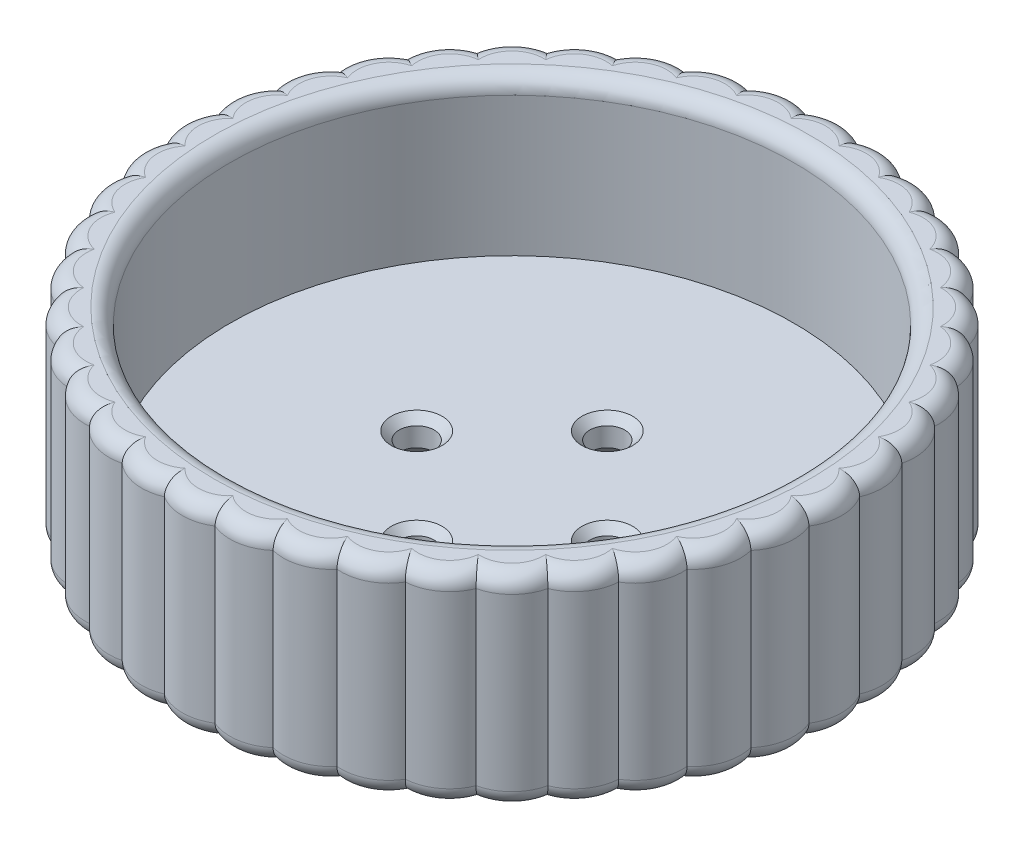
SolidWorks part; units mm, degrees
ref_plane "Front Plane" through (0, 0, 0) normal (0, 0, 1) x (1, 0, 0)
ref_plane "Top Plane" through (0, 0, 0) normal (0, 1, 0) x (1, 0, 0)
ref_plane "Right Plane" through (0, 0, 0) normal (1, 0, 0) x (0, 0, -1)
sketch "Sketch1" plane through (0, 0, 0) normal (0, 1, 0) x (1, 0, 0)
  line L0 (0, 0) -> (6, 0) construction
  line L1 (0, 0) -> (4.2426, 4.2426) construction
  arc A0 (-5.8992, -1.0954) -> (-1.0954, -5.8992) centre (0, 0) ccw
  circle A1 centre (0, 6) radius 1.1
  circle A2 centre (0, -6) radius 1.1
  circle A3 centre (-6, 0) radius 1.1
  circle A4 centre (6, 0) radius 1.1
  arc A5 (-1.0954, 5.8992) -> (-5.8992, 1.0954) centre (0, 0) ccw
  arc A6 (5.8992, 1.0954) -> (1.0954, 5.8992) centre (0, 0) ccw
  arc A7 (1.0954, -5.8992) -> (5.8992, -1.0954) centre (0, 0) ccw
  circle A8 centre (0, 0) radius 17.75
  circle A9 centre (0, 0) radius 20.75
  dimension "D1" = 3
extrude "Boss-Extrude1" add sketch "Sketch1" along normal blind 3 contours A8 A7 A2 A0 A3 A5 A1 A6 A4 | A2 A7 A4 A6 A1 A5 A3 A0 region at (0, 0, 0) region at (-17.248, 0, 0)
extrude "Boss-Extrude2" add sketch "Sketch1<6>" along normal blind 12.75 contours A9 A8 region at (-20.1631, 0, 0)
sketch "Sketch1<6>" plane through (0, 0, 0) normal (0, 1, 0) x (1, 0, 0) same geometry as "Sketch1"
chamfer "Chamfer1" distance 1.3 angle 45 4 edges at (-6, 0, 1.1) (0, 0, -4.9) (6, 0, 1.1) (0, 0, 7.1)
fillet "Fillet3" radius 1 1 edges at (0, 12.75, 17.75)
chamfer "Chamfer2" distance 0.5 angle 45 4 edges at (6, 3, 1.1) (0, 3, 7.1) (-6, 3, 1.1) (0, 3, -4.9)
sketch "Sketch3" plane through (0, 0, 0) normal (0, -1, 0) x (1, 0, 0)
  arc A0 (-12.3979, -12.7025) -> (-15.912, -7.8658) centre (-14.3601, -10.4332) ccw
  circle A1 centre (0, 0) radius 22
  arc A2 (-1.5968, -20.2897) -> (1.5968, -20.2897) centre (0, -17.75) ccw
  circle A3 centre (0, 0) radius 17.75
  arc A4 (-4.7512, -19.7901) -> (-1.5968, -20.2897) centre (-2.7767, -17.5315) ccw
  arc A5 (-7.7885, -18.8032) -> (-4.7512, -19.7901) centre (-5.4851, -16.8813) ccw
  arc A6 (-10.6341, -17.3533) -> (-7.7885, -18.8032) centre (-8.0583, -15.8154) ccw
  arc A7 (-13.2179, -15.4761) -> (-10.6341, -17.3533) centre (-10.4332, -14.3601) ccw
  arc A8 (-15.4761, -13.2179) -> (-13.2179, -15.4761) centre (-12.5511, -12.5511) ccw
  arc A9 (-17.3533, -10.6341) -> (-15.4761, -13.2179) centre (-14.3601, -10.4332) ccw
  arc A10 (-18.8032, -7.7885) -> (-17.3533, -10.6341) centre (-15.8154, -8.0583) ccw
  arc A11 (-19.7901, -4.7512) -> (-18.8032, -7.7885) centre (-16.8813, -5.4851) ccw
  arc A12 (-20.2897, -1.5968) -> (-19.7901, -4.7512) centre (-17.5315, -2.7767) ccw
  arc A13 (-20.2897, 1.5968) -> (-20.2897, -1.5968) centre (-17.75, 0) ccw
  arc A14 (-19.7901, 4.7512) -> (-20.2897, 1.5968) centre (-17.5315, 2.7767) ccw
  arc A15 (-18.8032, 7.7885) -> (-19.7901, 4.7512) centre (-16.8813, 5.4851) ccw
  arc A16 (-17.3533, 10.6341) -> (-18.8032, 7.7885) centre (-15.8154, 8.0583) ccw
  arc A17 (-15.4761, 13.2179) -> (-17.3533, 10.6341) centre (-14.3601, 10.4332) ccw
  arc A18 (-13.2179, 15.4761) -> (-15.4761, 13.2179) centre (-12.5511, 12.5511) ccw
  arc A19 (-10.6341, 17.3533) -> (-13.2179, 15.4761) centre (-10.4332, 14.3601) ccw
  arc A20 (-7.7885, 18.8032) -> (-10.6341, 17.3533) centre (-8.0583, 15.8154) ccw
  arc A21 (-4.7512, 19.7901) -> (-7.7885, 18.8032) centre (-5.4851, 16.8813) ccw
  arc A22 (-1.5968, 20.2897) -> (-4.7512, 19.7901) centre (-2.7767, 17.5315) ccw
  arc A23 (1.5968, 20.2897) -> (-1.5968, 20.2897) centre (0, 17.75) ccw
  arc A24 (4.7512, 19.7901) -> (1.5968, 20.2897) centre (2.7767, 17.5315) ccw
  arc A25 (7.7885, 18.8032) -> (4.7512, 19.7901) centre (5.4851, 16.8813) ccw
  arc A26 (10.6341, 17.3533) -> (7.7885, 18.8032) centre (8.0583, 15.8154) ccw
  arc A27 (13.2179, 15.4761) -> (10.6341, 17.3533) centre (10.4332, 14.3601) ccw
  arc A28 (15.4761, 13.2179) -> (13.2179, 15.4761) centre (12.5511, 12.5511) ccw
  arc A29 (17.3533, 10.6341) -> (15.4761, 13.2179) centre (14.3601, 10.4332) ccw
  arc A30 (18.8032, 7.7885) -> (17.3533, 10.6341) centre (15.8154, 8.0583) ccw
  arc A31 (19.7901, 4.7512) -> (18.8032, 7.7885) centre (16.8813, 5.4851) ccw
  arc A32 (16.8134, 5.6895) -> (17.7487, -0.2154) centre (17.5315, 2.7767) ccw
  arc A33 (17.4965, 2.9893) -> (17.4965, -2.9893) centre (17.75, 0) ccw
  arc A34 (19.7901, -4.7512) -> (20.2897, -1.5968) centre (17.5315, -2.7767) ccw
  arc A35 (18.8032, -7.7885) -> (19.7901, -4.7512) centre (16.8813, -5.4851) ccw
  arc A36 (17.3533, -10.6341) -> (18.8032, -7.7885) centre (15.8154, -8.0583) ccw
  arc A37 (15.4761, -13.2179) -> (17.3533, -10.6341) centre (14.3601, -10.4332) ccw
  arc A38 (13.2179, -15.4761) -> (15.4761, -13.2179) centre (12.5511, -12.5511) ccw
  arc A39 (10.6341, -17.3533) -> (13.2179, -15.4761) centre (10.4332, -14.3601) ccw
  arc A40 (10.6067, -14.2324) -> (5.2798, -16.9466) centre (8.0583, -15.8154) ccw
  arc A41 (4.7512, -19.7901) -> (7.7885, -18.8032) centre (5.4851, -16.8813) ccw
  arc A42 (1.5968, -20.2897) -> (4.7512, -19.7901) centre (2.7767, -17.5315) ccw
  arc A43 (15.7164, 8.2497) -> (17.5639, 2.5637) centre (16.8813, 5.4851) ccw
  arc A44 (14.2324, 10.6067) -> (16.9466, 5.2798) centre (15.8154, 8.0583) ccw
  arc A45 (12.3979, 12.7025) -> (15.912, 7.8658) centre (14.3601, 10.4332) ccw
  arc A46 (10.2581, 14.4856) -> (14.4856, 10.2581) centre (12.5511, 12.5511) ccw
  arc A47 (7.8658, 15.912) -> (12.7025, 12.3979) centre (10.4332, 14.3601) ccw
  arc A48 (5.2798, 16.9466) -> (10.6067, 14.2324) centre (8.0583, 15.8154) ccw
  arc A49 (2.5637, 17.5639) -> (8.2497, 15.7164) centre (5.4851, 16.8813) ccw
  arc A50 (-0.2154, 17.7487) -> (5.6895, 16.8134) centre (2.7767, 17.5315) ccw
  arc A51 (-2.9893, 17.4965) -> (2.9893, 17.4965) centre (0, 17.75) ccw
  arc A52 (-5.6895, 16.8134) -> (0.2154, 17.7487) centre (-2.7767, 17.5315) ccw
  arc A53 (-8.2497, 15.7164) -> (-2.5637, 17.5639) centre (-5.4851, 16.8813) ccw
  arc A54 (-10.6067, 14.2324) -> (-5.2798, 16.9466) centre (-8.0583, 15.8154) ccw
  arc A55 (-12.7025, 12.3979) -> (-7.8658, 15.912) centre (-10.4332, 14.3601) ccw
  arc A56 (-14.4856, 10.2581) -> (-10.2581, 14.4856) centre (-12.5511, 12.5511) ccw
  arc A57 (-15.912, 7.8658) -> (-12.3979, 12.7025) centre (-14.3601, 10.4332) ccw
  arc A58 (-16.9466, 5.2798) -> (-14.2324, 10.6067) centre (-15.8154, 8.0583) ccw
  arc A59 (-17.5639, 2.5637) -> (-15.7164, 8.2497) centre (-16.8813, 5.4851) ccw
  arc A60 (-17.7487, -0.2154) -> (-16.8134, 5.6895) centre (-17.5315, 2.7767) ccw
  arc A61 (-17.4965, -2.9893) -> (-17.4965, 2.9893) centre (-17.75, 0) ccw
  arc A62 (-16.8134, -5.6895) -> (-17.7487, 0.2154) centre (-17.5315, -2.7767) ccw
  arc A63 (-15.7164, -8.2497) -> (-17.5639, -2.5637) centre (-16.8813, -5.4851) ccw
  arc A64 (-14.2324, -10.6067) -> (-16.9466, -5.2798) centre (-15.8154, -8.0583) ccw
  arc A65 (-10.2581, -14.4856) -> (-14.4856, -10.2581) centre (-12.5511, -12.5511) ccw
  arc A66 (-7.8658, -15.912) -> (-12.7025, -12.3979) centre (-10.4332, -14.3601) ccw
  arc A67 (-5.2798, -16.9466) -> (-10.6067, -14.2324) centre (-8.0583, -15.8154) ccw
  arc A68 (-2.5637, -17.5639) -> (-8.2497, -15.7164) centre (-5.4851, -16.8813) ccw
  arc A69 (0.2154, -17.7487) -> (-5.6895, -16.8134) centre (-2.7767, -17.5315) ccw
  arc A70 (2.9893, -17.4965) -> (-2.9893, -17.4965) centre (0, -17.75) ccw
  arc A71 (5.6895, -16.8134) -> (-0.2154, -17.7487) centre (2.7767, -17.5315) ccw
  arc A72 (8.2497, -15.7164) -> (2.5637, -17.5639) centre (5.4851, -16.8813) ccw
  arc A73 (12.7025, -12.3979) -> (7.8658, -15.912) centre (10.4332, -14.3601) ccw
  arc A74 (7.7885, -18.8032) -> (10.6341, -17.3533) centre (8.0583, -15.8154) ccw
  arc A75 (14.4856, -10.2581) -> (10.2581, -14.4856) centre (12.5511, -12.5511) ccw
  arc A76 (15.912, -7.8658) -> (12.3979, -12.7025) centre (14.3601, -10.4332) ccw
  arc A77 (16.9466, -5.2798) -> (14.2324, -10.6067) centre (15.8154, -8.0583) ccw
  arc A78 (17.5639, -2.5637) -> (15.7164, -8.2497) centre (16.8813, -5.4851) ccw
  arc A79 (20.2897, -1.5968) -> (20.2897, 1.5968) centre (17.75, 0) ccw
  arc A80 (17.7487, 0.2154) -> (16.8134, -5.6895) centre (17.5315, -2.7767) ccw
  arc A81 (20.2897, 1.5968) -> (19.7901, 4.7512) centre (17.5315, 2.7767) ccw
  point P89 (0, 0)
  point P170 (0, 0)
  circle M51 centre (0, 0) radius 20.75
  dimension "D2" = 40
extrude "Cut-Extrude7" cut sketch "Sketch3" against normal up to surface (12.75 mm away) contours A24 A23 M51 | A23 A22 M51 | A22 A21 M51 | A21 A20 M51 | A20 A19 M51 | A19 A18 M51 | A18 A17 M51 | A17 A16 M51 | A16 A15 M51 | A15 A14 M51 | A14 A13 M51 | A13 A12 M51 | A12 A11 M51 | A11 A10 M51 | A10 A9 M51 | A9 A8 M51 | A8 A7 M51 | A7 A6 M51 | A6 A5 M51 | A4 A2 M51 | A42 A2 M51 | A5 A4 M51 | A74 A41 M51 | A42 A41 M51 | A74 A39 M51 | A39 A38 M51 | A38 A37 M51 | A37 A36 M51 | A36 A35 M51 | A35 A34 M51 | A79 A34 M51 | A81 A79 M51 | A81 A31 M51 | A30 A29 M51 | A31 A30 M51 | A29 A28 M51 | A28 A27 M51 | A26 A25 M51 | A25 A24 M51 | A27 A26 M51 region at (-1.6183, 0, -20.5623) region at (1.6183, 0, -20.5623) region at (-4.815, 0, -20.056) region at (4.815, 0, -20.056) region at (-7.8932, 0, -19.0558) region at (7.8932, 0, -19.0558) region at (-10.777, 0, -17.5865) region at (10.777, 0, -17.5865) region at (-13.3954, 0, -15.684) region at (13.3954, 0, -15.684) region at (-15.684, 0, -13.3954) region at (15.684, 0, -13.3954) region at (-17.5865, 0, -10.777) region at (17.5865, 0, -10.777) region at (-19.0558, 0, -7.8932) region at (19.0558, 0, -7.8932) region at (-20.056, 0, -4.815) region at (20.056, 0, -4.815) region at (-20.5623, 0, -1.6183) region at (20.5623, 0, -1.6183) region at (-20.5623, 0, 1.6183) region at (20.5623, 0, 1.6183) region at (-20.056, 0, 4.815) region at (20.056, 0, 4.815) region at (-19.0558, 0, 7.8932) region at (19.0558, 0, 7.8932) region at (-17.5865, 0, 10.777) region at (17.5865, 0, 10.777) region at (-15.684, 0, 13.3954) region at (15.684, 0, 13.3954) region at (-13.3954, 0, 15.684) region at (13.3954, 0, 15.684) region at (-10.777, 0, 17.5865) region at (10.777, 0, 17.5865) region at (-7.8932, 0, 19.0558) region at (7.8932, 0, 19.0558) region at (-4.815, 0, 20.056) region at (4.815, 0, 20.056) region at (-1.6183, 0, 20.5623) region at (1.6183, 0, 20.5623) up to face at (0, 12.75, 18.75)
fillet "Fillet7" radius 1 40 edges at (6.4121, 12.75, 19.7344) (3.246, 12.75, 20.4945) (0, 12.75, 20.75) (-3.246, 12.75, 20.4945) (-6.4121, 12.75, 19.7344) (-9.4203, 12.75, 18.4884) (-12.1965, 12.75, 16.7871) (-14.6725, 12.75, 14.6725) (-16.7871, 12.75, 12.1965) (-18.4884, 12.75, 9.4203) (-19.7344, 12.75, 6.4121) (-20.4945, 12.75, 3.246) (-20.75, 12.75, 0) (-20.4945, 12.75, -3.246) (-19.7344, 12.75, -6.4121) (-18.4884, 12.75, -9.4203) (-16.7871, 12.75, -12.1965) (-14.6725, 12.75, -14.6725) (-12.1965, 12.75, -16.7871) (-9.4203, 12.75, -18.4884) (-6.4121, 12.75, -19.7344) (-3.246, 12.75, -20.4945) (0, 12.75, -20.75) (3.246, 12.75, -20.4945) (6.4121, 12.75, -19.7344) (9.4203, 12.75, -18.4884) (12.1965, 12.75, -16.7871) (14.6725, 12.75, -14.6725) (16.7871, 12.75, -12.1965) (18.4884, 12.75, -9.4203) (19.7344, 12.75, -6.4121) (20.4945, 12.75, -3.246) (20.75, 12.75, 0) (20.4945, 12.75, 3.246) (19.7344, 12.75, 6.4121) (18.4884, 12.75, 9.4203) (16.7871, 12.75, 12.1965) (14.6725, 12.75, 14.6725) (12.1965, 12.75, 16.7871) (9.4203, 12.75, 18.4884)
fillet "Fillet8" radius 1 40 edges at (16.7871, 0, -12.1965) (14.6725, 0, -14.6725) (12.1965, 0, -16.7871) (9.4203, 0, -18.4884) (6.4121, 0, -19.7344) (3.246, 0, -20.4945) (0, 0, -20.75) (-3.246, 0, -20.4945) (-6.4121, 0, -19.7344) (-9.4203, 0, -18.4884) (-12.1965, 0, -16.7871) (-14.6725, 0, -14.6725) (-16.7871, 0, -12.1965) (-18.4884, 0, -9.4203) (-19.7344, 0, -6.4121) (-20.4945, 0, -3.246) (-20.75, 0, 0) (-20.4945, 0, 3.246) (-19.7344, 0, 6.4121) (-18.4884, 0, 9.4203) (-16.7871, 0, 12.1965) (-14.6725, 0, 14.6725) (18.4884, 0, -9.4203) (19.7344, 0, -6.4121) (20.4945, 0, -3.246) (20.4945, 0, 3.246) (20.75, 0, 0) (19.7344, 0, 6.4121) (18.4884, 0, 9.4203) (16.7871, 0, 12.1965) (14.6725, 0, 14.6725) (12.1965, 0, 16.7871) (9.4203, 0, 18.4884) (6.4121, 0, 19.7344) (3.246, 0, 20.4945) (0, 0, 20.75) (-3.246, 0, 20.4945) (-6.4121, 0, 19.7344) (-9.4203, 0, 18.4884) (-12.1965, 0, 16.7871)
